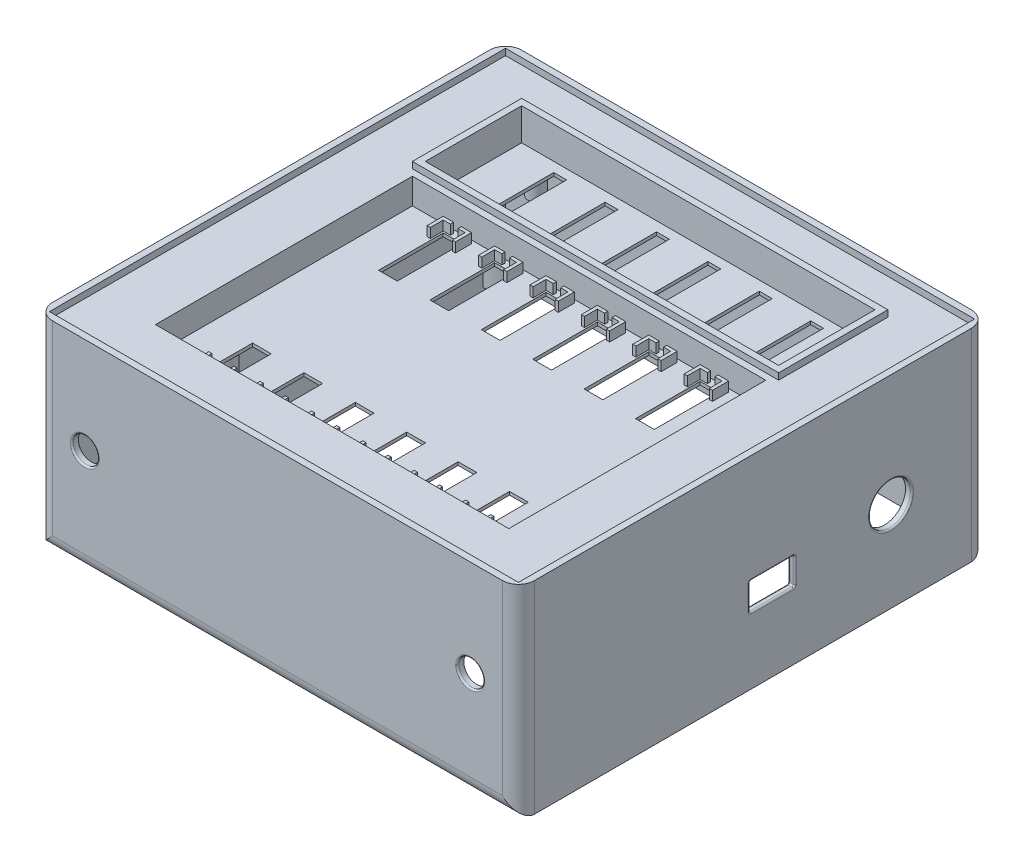
SolidWorks part; units mm, degrees
ref_plane "Front Plane" through (0, 0, 0) normal (0, 0, 1) x (1, 0, 0)
ref_plane "Top Plane" through (0, 0, 0) normal (0, 1, 0) x (1, 0, 0)
ref_plane "Right Plane" through (0, 0, 0) normal (1, 0, 0) x (0, 0, -1)
sketch "Sketch1" plane through (0, 0, 0) normal (0, 1, 0) x (1, 0, 0)
  line L1 (75, -65.5) -> (-75, -65.5)
  line L2 (75, -65.5) -> (75, 65.5)
  line L3 (75, 65.5) -> (-75, 65.5)
  line L4 (-75, -65.5) -> (-75, 65.5)
  line L5 (75, -65.5) -> (-75, 65.5) construction
  line L6 (75, 65.5) -> (-75, -65.5) construction
  point P0 (0, 0)
  dimension "D1" = 150
  dimension "D2" = 131
extrude "Boss-Extrude1" add sketch "Sketch1" against normal blind 63
sketch "Sketch2" plane through (0, 0, 0) normal (0, 1, 0) x (1, 0, 0)
  line L0 (0, -71.4639) -> (0, 67.3904) construction
  line L1 (75, 65.5) -> (-75, 65.5) construction
  line L2 (55, 20.5) -> (-55, 20.5)
  line L3 (55, 20.5) -> (55, 50.5)
  line L4 (55, 50.5) -> (-55, 50.5)
  line L5 (-55, 20.5) -> (-55, 50.5)
  line L6 (55, 20.5) -> (-55, 50.5) construction
  line L7 (55, 50.5) -> (-55, 20.5) construction
  point P2 (0, 35.5)
  dimension "D1" = 30
  dimension "D2" = 110
  dimension "D3" = 15
extrude "Cut-Extrude1" cut sketch "Sketch2" against normal blind 10
sketch "Sketch3" plane through (0, 0, 0) normal (0, 1, 0) x (1, 0, 0)
  line L0 (-73, 63.5) -> (-73, -63.5)
  line L1 (-73, -63.5) -> (73, -63.5)
  line L2 (73, -63.5) -> (73, 63.5)
  line L3 (73, 63.5) -> (-73, 63.5)
  line L8 (-75, 65.5) -> (-75, -65.5) construction
  line L9 (75, 65.5) -> (-75, 65.5) construction
  line L10 (75, -65.5) -> (75, 65.5) construction
  line L11 (-75, -65.5) -> (75, -65.5) construction
  line L12 (-57, 18.5) -> (57, 18.5)
  line L13 (57, 18.5) -> (57, 52.5)
  line L14 (57, 52.5) -> (-57, 52.5)
  line L15 (-57, 52.5) -> (-57, 18.5)
  line L18 (55, 50.5) -> (-55, 50.5) construction
  line L19 (-55, 50.5) -> (-55, 20.5) construction
  line L20 (-55, 20.5) -> (55, 20.5) construction
  line L21 (55, 20.5) -> (55, 50.5) construction
  dimension "D1" = 2
  dimension "D2" = 2
  dimension "D3" = 2
  dimension "D4" = 2
  dimension "D5" = 2
  dimension "D6" = 2
  dimension "D7" = 2
  dimension "D8" = 2
extrude "Cut-Extrude2" cut sketch "Sketch3" against normal blind 2
sketch "Sketch5" plane through (0, -2, 0) normal (0, 1, 0) x (1, 0, 0)
  line L0 (75, -65.5) -> (75, 65.5) construction
  line L1 (55, -63.5) -> (-55, -63.5)
  line L2 (55, -63.5) -> (55, 16.5)
  line L3 (55, 16.5) -> (-55, 16.5)
  line L4 (-55, -63.5) -> (-55, 16.5)
  line L5 (55, -63.5) -> (-55, 16.5) construction
  line L6 (55, 16.5) -> (-55, -63.5) construction
  line L7 (-75, 65.5) -> (-75, -65.5) construction
  line L8 (-73, -63.5) -> (73, -63.5) construction
  point P0 (0, -23.5)
  dimension "D1" = 80
  dimension "D2" = 110
  dimension "D3" = 20
  dimension "D4" = 20
  dimension "D5" = 0
extrude "Cut-Extrude3" cut sketch "Sketch5" against normal blind 8
sketch "Sketch6" plane through (0, -63, 0) normal (0, -1, 0) x (1, 0, 0)
  line L0 (75, 65.5) -> (75, -65.5) construction
  line L1 (-73, 63.5) -> (73, 63.5)
  line L2 (-73, 63.5) -> (-73, -63.5)
  line L3 (-73, -63.5) -> (73, -63.5)
  line L4 (73, 63.5) -> (73, -63.5)
  line L5 (-73, 63.5) -> (73, -63.5) construction
  line L6 (-73, -63.5) -> (73, 63.5) construction
  line L7 (75, -65.5) -> (-75, -65.5) construction
  point P0 (0, 0)
  dimension "D1" = 2
  dimension "D2" = 2
extrude "Cut-Extrude4" cut sketch "Sketch6" against normal blind 52
sketch "Sketch7" plane through (0, -10, 0) normal (0, 1, 0) x (1, 0, 0)
  line L0 (-55, 50.5) -> (-55, 20.5) construction
  line L1 (-42, 47.5) -> (-38, 47.5)
  line L2 (-42, 47.5) -> (-42, 22.5)
  line L3 (-42, 22.5) -> (-38, 22.5)
  line L4 (-38, 47.5) -> (-38, 22.5)
  line L5 (55, 50.5) -> (-55, 50.5) construction
  line L6 (55, 50.5) -> (-55, 50.5) construction
  line L7 (-26, 47.5) -> (-22, 47.5)
  line L8 (-26, 47.5) -> (-26, 22.5)
  line L9 (-26, 22.5) -> (-22, 22.5)
  line L10 (-22, 47.5) -> (-22, 22.5)
  line L11 (-10, 47.5) -> (-6, 47.5)
  line L12 (-10, 47.5) -> (-10, 22.5)
  line L13 (-10, 22.5) -> (-6, 22.5)
  line L14 (-6, 47.5) -> (-6, 22.5)
  line L15 (6, 47.5) -> (10, 47.5)
  line L16 (6, 47.5) -> (6, 22.5)
  line L17 (6, 22.5) -> (10, 22.5)
  line L18 (10, 47.5) -> (10, 22.5)
  line L19 (22, 47.5) -> (26, 47.5)
  line L20 (22, 47.5) -> (22, 22.5)
  line L21 (22, 22.5) -> (26, 22.5)
  line L22 (26, 47.5) -> (26, 22.5)
  line L23 (38, 47.5) -> (42, 47.5)
  line L24 (38, 47.5) -> (38, 22.5)
  line L25 (38, 22.5) -> (42, 22.5)
  line L26 (42, 47.5) -> (42, 22.5)
  dimension "D1" = 13
  dimension "D2" = 4
  dimension "D3" = 3
  dimension "D4" = 25
  dimension "D5" = 12
  dimension "D6" = 4
  dimension "D7" = 25
  dimension "D8" = 3
  dimension "D9" = 4
  dimension "D10" = 25
  dimension "D11" = 3
  dimension "D12" = 25
  dimension "D13" = 12
  dimension "D14" = 12
  dimension "D15" = 4
  dimension "D16" = 3
  dimension "D17" = 25
  dimension "D18" = 12
  dimension "D19" = 4
  dimension "D20" = 25
  dimension "D21" = 3
  dimension "D22" = 12
  dimension "D23" = 4
  dimension "D24" = 4
  dimension "D25" = 3
  dimension "D26" = 25
extrude "Cut-Extrude5" cut sketch "Sketch7" against normal blind 1.2
sketch "Sketch8" plane through (0, -10, 0) normal (0, 1, 0) x (1, 0, 0)
  line L0 (-40, 9.5911) -> (-40, -52.7056) construction
  line L1 (-24, 9.5911) -> (-24, -53.8329) construction
  line L2 (-8, 9.5911) -> (-8, -53.8329) construction
  line L3 (8, 9.5911) -> (8, -53.8329) construction
  line L4 (24, 9.5911) -> (24, -53.8329) construction
  line L5 (40, 9.5911) -> (40, -53.8329) construction
  line L6 (-49.171, -23.5) -> (50.2417, -23.5) construction
  line L7 (-73, -63.5) -> (73, -63.5) construction
  line L8 (-42.9103, -61) -> (-37.0897, -61)
  line L9 (-42.9103, -61) -> (-42.9103, -45.3557)
  line L10 (-42.9103, 14) -> (-37.0897, 14)
  line L11 (-37.0897, -61) -> (-37.0897, -45.3557)
  line L12 (-42.9103, -61) -> (-37.0897, 14) construction
  line L13 (-42.9103, 14) -> (-37.0897, -61) construction
  line L14 (-42.9103, -6.1263) -> (-37.0897, -6.1263)
  line L15 (-42.9103, -45.3557) -> (-37.0897, -45.3557)
  line L16 (-37.0897, -6.1263) -> (-37.0897, 14)
  line L17 (-42.9103, -6.1263) -> (-42.9103, 14)
  line L18 (-32, 9.5911) -> (-32, -46.68) construction
  line L19 (-21.0897, -61) -> (-21.0897, -45.3557)
  line L20 (-21.0897, -45.3557) -> (-26.9103, -45.3557)
  line L21 (-26.9103, -61) -> (-26.9103, -45.3557)
  line L22 (-21.0897, -61) -> (-26.9103, -61)
  line L23 (-21.0897, -6.1263) -> (-21.0897, 14)
  line L24 (-21.0897, -6.1263) -> (-26.9103, -6.1263)
  line L25 (-26.9103, -6.1263) -> (-26.9103, 14)
  line L26 (-21.0897, 14) -> (-26.9103, 14)
  line L27 (-16, 9.5911) -> (-16, -45.3557) construction
  line L28 (0, 9.5911) -> (0, -45.3557) construction
  line L29 (-10.9103, -61) -> (-5.0897, -61)
  line L30 (-5.0897, -61) -> (-5.0897, -45.3557)
  line L31 (-10.9103, -45.3557) -> (-5.0897, -45.3557)
  line L32 (-10.9103, -61) -> (-10.9103, -45.3557)
  line L33 (-10.9103, -6.1263) -> (-5.0897, -6.1263)
  line L34 (-5.0897, -6.1263) -> (-5.0897, 14)
  line L35 (-10.9103, 14) -> (-5.0897, 14)
  line L36 (-10.9103, -6.1263) -> (-10.9103, 14)
  line L37 (10.9103, -61) -> (10.9103, -45.3557)
  line L38 (10.9103, -45.3557) -> (5.0897, -45.3557)
  line L39 (5.0897, -61) -> (5.0897, -45.3557)
  line L40 (10.9103, -61) -> (5.0897, -61)
  line L41 (21.0897, -61) -> (26.9103, -61)
  line L42 (26.9103, -61) -> (26.9103, -45.3557)
  line L43 (21.0897, -45.3557) -> (26.9103, -45.3557)
  line L44 (21.0897, -61) -> (21.0897, -45.3557)
  line L45 (42.9103, -61) -> (42.9103, -45.3557)
  line L46 (42.9103, -45.3557) -> (37.0897, -45.3557)
  line L47 (37.0897, -61) -> (37.0897, -45.3557)
  line L48 (42.9103, -61) -> (37.0897, -61)
  line L49 (10.9103, -6.1263) -> (10.9103, 14)
  line L50 (10.9103, 14) -> (5.0897, 14)
  line L51 (5.0897, -6.1263) -> (5.0897, 14)
  line L52 (10.9103, -6.1263) -> (5.0897, -6.1263)
  line L53 (21.0897, -6.1263) -> (26.9103, -6.1263)
  line L54 (26.9103, -6.1263) -> (26.9103, 14)
  line L55 (21.0897, 14) -> (26.9103, 14)
  line L56 (21.0897, -6.1263) -> (21.0897, 14)
  line L57 (42.9103, -6.1263) -> (42.9103, 14)
  line L58 (42.9103, -6.1263) -> (37.0897, -6.1263)
  line L59 (37.0897, -6.1263) -> (37.0897, 14)
  line L60 (42.9103, 14) -> (37.0897, 14)
  point P14 (-40, -23.5)
  dimension "D1" = 75
  dimension "D2" = 40
  dimension "D3" = 8
  dimension "D4" = 8
  dimension "D5" = 8
extrude "Cut-Extrude6" cut sketch "Sketch8" against normal blind 1.2
sketch "Sketch9" plane through (0, -10, 0) normal (0, 1, 0) x (1, 0, 0)
  line L0 (-41.1603, 14.5) -> (-43.4103, 14.5)
  line L1 (-43.4103, 14.5) -> (-43.4103, 10.5)
  line L2 (-43.4103, 10.5) -> (-44.4103, 10.5)
  line L3 (-44.4103, 10.5) -> (-44.4103, 15.5)
  line L4 (-44.4103, 15.5) -> (-41.1603, 15.5)
  line L5 (-41.1603, 15.5) -> (-41.1603, 14.5)
  line L6 (-37.0897, 14) -> (-42.9103, 14) construction
  line L7 (-42.9103, 14) -> (-42.9103, -6.1263) construction
  line L8 (-40, -6.1263) -> (-40, 9.5642) construction
  line L9 (-42.9103, -6.1263) -> (-37.0897, -6.1263) construction
  line L10 (-24, 10.5) -> (-24, -7.9868) construction
  line L11 (-8, 10.5) -> (-8, -9.2113) construction
  line L12 (-32, 9.5642) -> (-32, -3.0888) construction
  line L13 (-16, 9.5642) -> (-16, -3.6136) construction
  line L14 (-44.4103, -23.5) -> (49.8597, -23.5) construction
  line L15 (-55, -63.5) -> (55, -63.5) construction
  line L16 (-35.5897, 15.5) -> (-38.8397, 15.5)
  line L17 (-35.5897, 10.5) -> (-35.5897, 15.5)
  line L18 (-36.5897, 10.5) -> (-35.5897, 10.5)
  line L19 (-36.5897, 14.5) -> (-36.5897, 10.5)
  line L20 (-38.8397, 14.5) -> (-36.5897, 14.5)
  line L21 (-38.8397, 15.5) -> (-38.8397, 14.5)
  line L22 (-44.4103, -62.5) -> (-41.1603, -62.5)
  line L23 (-44.4103, -57.5) -> (-44.4103, -62.5)
  line L24 (-43.4103, -57.5) -> (-44.4103, -57.5)
  line L25 (-43.4103, -61.5) -> (-43.4103, -57.5)
  line L26 (-41.1603, -61.5) -> (-43.4103, -61.5)
  line L27 (-41.1603, -62.5) -> (-41.1603, -61.5)
  line L28 (-35.5897, -57.5) -> (-35.5897, -62.5)
  line L29 (-36.5897, -57.5) -> (-35.5897, -57.5)
  line L30 (-36.5897, -61.5) -> (-36.5897, -57.5)
  line L31 (-38.8397, -61.5) -> (-36.5897, -61.5)
  line L32 (-38.8397, -62.5) -> (-38.8397, -61.5)
  line L33 (-35.5897, -62.5) -> (-38.8397, -62.5)
  line L34 (-19.5897, -57.5) -> (-19.5897, -62.5)
  line L35 (-20.5897, -57.5) -> (-19.5897, -57.5)
  line L36 (-20.5897, -61.5) -> (-20.5897, -57.5)
  line L37 (-22.8397, -61.5) -> (-20.5897, -61.5)
  line L38 (-22.8397, -62.5) -> (-22.8397, -61.5)
  line L39 (-19.5897, -62.5) -> (-22.8397, -62.5)
  line L40 (-27.4103, -57.5) -> (-28.4103, -57.5)
  line L41 (-27.4103, -61.5) -> (-27.4103, -57.5)
  line L42 (-25.1603, -61.5) -> (-27.4103, -61.5)
  line L43 (-25.1603, -62.5) -> (-25.1603, -61.5)
  line L44 (-28.4103, -62.5) -> (-25.1603, -62.5)
  line L45 (-28.4103, -57.5) -> (-28.4103, -62.5)
  line L46 (-19.5897, 15.5) -> (-22.8397, 15.5)
  line L47 (-19.5897, 10.5) -> (-19.5897, 15.5)
  line L48 (-20.5897, 10.5) -> (-19.5897, 10.5)
  line L49 (-20.5897, 14.5) -> (-20.5897, 10.5)
  line L50 (-22.8397, 14.5) -> (-20.5897, 14.5)
  line L51 (-22.8397, 15.5) -> (-22.8397, 14.5)
  line L52 (-28.4103, 10.5) -> (-28.4103, 15.5)
  line L53 (-27.4103, 10.5) -> (-28.4103, 10.5)
  line L54 (-27.4103, 14.5) -> (-27.4103, 10.5)
  line L55 (-25.1603, 14.5) -> (-27.4103, 14.5)
  line L56 (-25.1603, 15.5) -> (-25.1603, 14.5)
  line L57 (-28.4103, 15.5) -> (-25.1603, 15.5)
  line L58 (-11.4103, -57.5) -> (-12.4103, -57.5)
  line L59 (-11.4103, -61.5) -> (-11.4103, -57.5)
  line L60 (-9.1603, -61.5) -> (-11.4103, -61.5)
  line L61 (-9.1603, -62.5) -> (-9.1603, -61.5)
  line L62 (-12.4103, -62.5) -> (-9.1603, -62.5)
  line L63 (-12.4103, -57.5) -> (-12.4103, -62.5)
  line L64 (-4.5897, -61.5) -> (-4.5897, -57.5)
  line L65 (-6.8397, -61.5) -> (-4.5897, -61.5)
  line L66 (-6.8397, -62.5) -> (-6.8397, -61.5)
  line L67 (-3.5897, -62.5) -> (-6.8397, -62.5)
  line L68 (-3.5897, -57.5) -> (-3.5897, -62.5)
  line L69 (-4.5897, -57.5) -> (-3.5897, -57.5)
  line L70 (-12.4103, 10.5) -> (-12.4103, 15.5)
  line L71 (-11.4103, 10.5) -> (-12.4103, 10.5)
  line L72 (-11.4103, 14.5) -> (-11.4103, 10.5)
  line L73 (-9.1603, 14.5) -> (-11.4103, 14.5)
  line L74 (-9.1603, 15.5) -> (-9.1603, 14.5)
  line L75 (-12.4103, 15.5) -> (-9.1603, 15.5)
  line L76 (-4.5897, 10.5) -> (-3.5897, 10.5)
  line L77 (-4.5897, 14.5) -> (-4.5897, 10.5)
  line L78 (-6.8397, 14.5) -> (-4.5897, 14.5)
  line L79 (-6.8397, 15.5) -> (-6.8397, 14.5)
  line L80 (-3.5897, 15.5) -> (-6.8397, 15.5)
  line L81 (-3.5897, 10.5) -> (-3.5897, 15.5)
  line L82 (0, -55) -> (0, 55) construction
  line L83 (6.8397, -61.5) -> (4.5897, -61.5)
  line L84 (6.8397, -62.5) -> (6.8397, -61.5)
  line L85 (3.5897, -62.5) -> (6.8397, -62.5)
  line L86 (3.5897, -57.5) -> (3.5897, -62.5)
  line L87 (4.5897, -57.5) -> (3.5897, -57.5)
  line L88 (4.5897, -61.5) -> (4.5897, -57.5)
  line L89 (11.4103, -61.5) -> (11.4103, -57.5)
  line L90 (9.1603, -61.5) -> (11.4103, -61.5)
  line L91 (9.1603, -62.5) -> (9.1603, -61.5)
  line L92 (12.4103, -62.5) -> (9.1603, -62.5)
  line L93 (12.4103, -57.5) -> (12.4103, -62.5)
  line L94 (11.4103, -57.5) -> (12.4103, -57.5)
  line L95 (20.5897, -57.5) -> (19.5897, -57.5)
  line L96 (20.5897, -61.5) -> (20.5897, -57.5)
  line L97 (22.8397, -61.5) -> (20.5897, -61.5)
  line L98 (22.8397, -62.5) -> (22.8397, -61.5)
  line L99 (19.5897, -62.5) -> (22.8397, -62.5)
  line L100 (19.5897, -57.5) -> (19.5897, -62.5)
  line L101 (27.4103, -61.5) -> (27.4103, -57.5)
  line L102 (25.1603, -61.5) -> (27.4103, -61.5)
  line L103 (25.1603, -62.5) -> (25.1603, -61.5)
  line L104 (28.4103, -62.5) -> (25.1603, -62.5)
  line L105 (28.4103, -57.5) -> (28.4103, -62.5)
  line L106 (27.4103, -57.5) -> (28.4103, -57.5)
  line L107 (36.5897, -57.5) -> (35.5897, -57.5)
  line L108 (36.5897, -61.5) -> (36.5897, -57.5)
  line L109 (38.8397, -61.5) -> (36.5897, -61.5)
  line L110 (38.8397, -62.5) -> (38.8397, -61.5)
  line L111 (35.5897, -62.5) -> (38.8397, -62.5)
  line L112 (35.5897, -57.5) -> (35.5897, -62.5)
  line L113 (44.4103, -57.5) -> (44.4103, -62.5)
  line L114 (43.4103, -57.5) -> (44.4103, -57.5)
  line L115 (43.4103, -61.5) -> (43.4103, -57.5)
  line L116 (41.1603, -61.5) -> (43.4103, -61.5)
  line L117 (41.1603, -62.5) -> (41.1603, -61.5)
  line L118 (44.4103, -62.5) -> (41.1603, -62.5)
  line L119 (4.5897, 14.5) -> (4.5897, 10.5)
  line L120 (6.8397, 14.5) -> (4.5897, 14.5)
  line L121 (6.8397, 15.5) -> (6.8397, 14.5)
  line L122 (3.5897, 15.5) -> (6.8397, 15.5)
  line L123 (3.5897, 10.5) -> (3.5897, 15.5)
  line L124 (4.5897, 10.5) -> (3.5897, 10.5)
  line L125 (11.4103, 10.5) -> (12.4103, 10.5)
  line L126 (11.4103, 14.5) -> (11.4103, 10.5)
  line L127 (9.1603, 14.5) -> (11.4103, 14.5)
  line L128 (9.1603, 15.5) -> (9.1603, 14.5)
  line L129 (12.4103, 15.5) -> (9.1603, 15.5)
  line L130 (12.4103, 10.5) -> (12.4103, 15.5)
  line L131 (19.5897, 10.5) -> (19.5897, 15.5)
  line L132 (20.5897, 10.5) -> (19.5897, 10.5)
  line L133 (20.5897, 14.5) -> (20.5897, 10.5)
  line L134 (22.8397, 14.5) -> (20.5897, 14.5)
  line L135 (22.8397, 15.5) -> (22.8397, 14.5)
  line L136 (19.5897, 15.5) -> (22.8397, 15.5)
  line L137 (27.4103, 10.5) -> (28.4103, 10.5)
  line L138 (27.4103, 14.5) -> (27.4103, 10.5)
  line L139 (25.1603, 14.5) -> (27.4103, 14.5)
  line L140 (25.1603, 15.5) -> (25.1603, 14.5)
  line L141 (28.4103, 15.5) -> (25.1603, 15.5)
  line L142 (28.4103, 10.5) -> (28.4103, 15.5)
  line L143 (35.5897, 10.5) -> (35.5897, 15.5)
  line L144 (36.5897, 10.5) -> (35.5897, 10.5)
  line L145 (36.5897, 14.5) -> (36.5897, 10.5)
  line L146 (38.8397, 14.5) -> (36.5897, 14.5)
  line L147 (38.8397, 15.5) -> (38.8397, 14.5)
  line L148 (35.5897, 15.5) -> (38.8397, 15.5)
  line L149 (44.4103, 15.5) -> (41.1603, 15.5)
  line L150 (44.4103, 10.5) -> (44.4103, 15.5)
  line L151 (43.4103, 10.5) -> (44.4103, 10.5)
  line L152 (43.4103, 14.5) -> (43.4103, 10.5)
  line L153 (41.1603, 14.5) -> (43.4103, 14.5)
  line L154 (41.1603, 15.5) -> (41.1603, 14.5)
  dimension "D1" = 0.5
  dimension "D2" = 0.5
  dimension "D3" = 1
  dimension "D4" = 1
  dimension "D5" = 3.25
  dimension "D6" = 5
  dimension "D7" = 8
  dimension "D8" = 8
  dimension "D9" = 8
  dimension "D10" = 8
  dimension "D11" = 40
extrude "Boss-Extrude2" add sketch "Sketch9" along normal blind 3
sketch "Sketch10" plane through (0, -11, 0) normal (0, -1, 0) x (1, 0, 0)
  circle A0 centre (48, -48) radius 2.5
  circle A1 centre (-48, -48) radius 2.5
  circle A2 centre (48, 48) radius 2.5
  circle A3 centre (-48, 48) radius 2.5
  dimension "D5" = 5
  dimension "D8" = 5
  dimension "D11" = 5
  dimension "D14" = 5
extrude "Boss-Extrude3" add sketch "Sketch10" along normal blind 8.5
fillet "Fillet1" radius 2 1 edges at (48, -11, -50.5)
fillet "Fillet2" radius 2 3 edges at (48, -11, 45.5) (-48, -11, 45.5) (-48, -11, -50.5)
sketch "Sketch11" plane through (0, -19.5, 0) normal (0, -1, 0) x (1, 0, 0)
  circle A0 centre (48, -48) radius 1.5
  dimension "D1" = 3
extrude "Cut-Extrude7" cut sketch "Sketch11" against normal blind 5
mirror "Mirror1" about plane through (0, 0, 0) normal (1, 0, 0) of "Cut-Extrude7"
sketch "Sketch12" plane through (0, -19.5, 0) normal (0, -1, 0) x (1, 0, 0)
  circle A0 centre (48, 48) radius 1.5
  dimension "D1" = 3
extrude "Cut-Extrude8" cut sketch "Sketch12" against normal blind 5
mirror "Mirror3" about plane through (0, 0, 0) normal (1, 0, 0) of "Cut-Extrude8"
sketch "Sketch13" plane through (0, 0, 0) normal (0, 1, 0) x (1, 0, 0)
  line L1 (75, -65.5) -> (-75, -65.5)
  line L2 (75, -65.5) -> (75, -80.5)
  line L3 (75, -80.5) -> (-75, -80.5)
  line L4 (-75, -65.5) -> (-75, -80.5)
  dimension "D1" = 15
  dimension "D2" = 150
extrude "Boss-Extrude4" add sketch "Sketch13" against normal blind 63
sketch "Sketch14" plane through (0, 0, 0) normal (0, 1, 0) x (1, 0, 0)
  line L1 (73, -63.5) -> (-73, -63.5)
  line L2 (73, -63.5) -> (73, -78.5)
  line L3 (73, -78.5) -> (-73, -78.5)
  line L4 (-73, -63.5) -> (-73, -78.5)
  dimension "D1" = 15
  dimension "D2" = 146
extrude "Cut-Extrude9" cut sketch "Sketch14" against normal blind 2
sketch "Sketch15" plane through (0, -63, 0) normal (0, -1, 0) x (1, 0, 0)
  line L1 (-73, 63.5) -> (73, 63.5)
  line L2 (-73, 63.5) -> (-73, 78.5)
  line L3 (-73, 78.5) -> (73, 78.5)
  line L4 (73, 63.5) -> (73, 78.5)
  dimension "D1" = 15
  dimension "D2" = 146
extrude "Cut-Extrude10" cut sketch "Sketch15" against normal blind 52
sketch "Sketch17" plane through (0, -63, 0) normal (0, -1, 0) x (1, 0, 0)
  line L0 (73, -63.5) -> (73, 78.5) construction
  line L1 (-73, -63.5) -> (73, -63.5) construction
  line L2 (73, -63.5) -> (66, -63.5)
  line L3 (73, -63.5) -> (73, -56.5)
  line L4 (-73, 78.5) -> (-73, -63.5) construction
  line L5 (-73, -63.5) -> (73, -63.5) construction
  line L6 (-66, -63.5) -> (-73, -63.5)
  line L7 (-73, -63.5) -> (-73, -56.5)
  line L8 (73, 78.5) -> (-73, 78.5) construction
  line L9 (-66, 78.5) -> (-73, 78.5)
  line L10 (-73, 78.5) -> (-73, 71.5)
  line L11 (73, 78.5) -> (73, 71.5)
  line L12 (73, 78.5) -> (66, 78.5)
  arc A0 (73, -56.5) -> (66, -63.5) centre (73, -63.5) ccw
  arc A1 (-73, -56.5) -> (-66, -63.5) centre (-73, -63.5) cw
  arc A2 (-73, 71.5) -> (-66, 78.5) centre (-73, 78.5) ccw
  arc A3 (73, 71.5) -> (66, 78.5) centre (73, 78.5) cw
  dimension "D1" = 7
  dimension "D2" = 7
  dimension "D3" = 7
  dimension "D4" = 7
extrude "Boss-Extrude5" add sketch "Sketch17" against normal blind 10
sketch "Sketch18" plane through (0, -63, 0) normal (0, -1, 0) x (1, 0, 0)
  line L0 (-73, -63.5) -> (73, -63.5) construction
  line L1 (73, -63.5) -> (-73, -63.5)
  line L2 (73, -63.5) -> (73, 78.5)
  line L3 (73, 78.5) -> (-73, 78.5)
  line L4 (-73, -63.5) -> (-73, 78.5)
  line L5 (-73, 78.5) -> (-73, -63.5) construction
  line L6 (66, 78.5) -> (-66, 78.5) construction
  line L7 (73, -56.5) -> (73, 71.5) construction
  dimension "D1" = 0
  dimension "D2" = 0
  dimension "D3" = 0
extrude "Cut-Extrude11" cut sketch "Sketch18" against normal blind 2
sketch "Sketch19" plane through (0, -61, 0) normal (0, -1, 0) x (1, 0, 0)
  line L0 (-73, -63.5) -> (73, -63.5) construction
  line L1 (73, -63.5) -> (73, 78.5) construction
  circle A0 centre (70, -60.5) radius 1.5
  dimension "D1" = 3
  dimension "D2" = 3
  dimension "D3" = 3
extrude "Cut-Extrude12" cut sketch "Sketch19" against normal blind 5
sketch "Sketch20" plane through (0, -61, 0) normal (0, -1, 0) x (1, 0, 0)
  line L0 (-73, -63.5) -> (-66, -63.5) construction
  line L3 (-73, 78.5) -> (-73, -63.5) construction
  line L4 (-66, 78.5) -> (-73, 78.5) construction
  line L6 (-73, 78.5) -> (-73, 71.5) construction
  line L7 (73, 78.5) -> (66, 78.5) construction
  line L9 (73, -63.5) -> (73, 78.5) construction
  circle A0 centre (-70, -60.5) radius 1.5
  circle A1 centre (-70, 75.5) radius 1.5
  circle A2 centre (70, 75.5) radius 1.5
  dimension "D1" = 3
  dimension "D4" = 3
  dimension "D7" = 3
  dimension "D2" = 3
  dimension "D3" = 3
  dimension "D5" = 3
  dimension "D6" = 3
  dimension "D8" = 3
  dimension "D9" = 3
sketch "Sketch21" plane through (75, 0, 0) normal (1, 0, 0) x (0, 0, -1)
  line L0 (65.5, -63) -> (65.5, 0) construction
  line L1 (-80.5, 0) -> (65.5, 0) construction
  circle A0 centre (35.5, -35) radius 6.5
  dimension "D1" = 13
  dimension "D2" = 30
  dimension "D3" = 35
extrude "Cut-Extrude14" cut sketch "Sketch21" against normal blind 5
fillet "Fillet3" radius 0.5 1 edges at (75, -35, -42)
sketch "Sketch22" plane through (0, 0, 80.5) normal (0, 0, 1) x (1, 0, 0)
  line L0 (75, -63) -> (75, 0) construction
  line L1 (-75, -63) -> (-75, 0) construction
  line L2 (-75, 0) -> (75, 0) construction
  circle A0 centre (60, -30) radius 4
  circle A1 centre (-60, -30) radius 4
  dimension "D1" = 8
  dimension "D2" = 8
  dimension "D3" = 15
  dimension "D4" = 15
  dimension "D5" = 30
  dimension "D6" = 30
extrude "Cut-Extrude15" cut sketch "Sketch22" against normal blind 5
fillet "Fillet4" radius 0.5 2 edges at (-56, -30, 80.5) (64, -30, 80.5)
sketch "Sketch23" plane through (75, 0, 0) normal (1, 0, 0) x (0, 0, -1)
  line L1 (-8.5, -42.25) -> (5.5, -42.25)
  line L2 (-8.5, -42.25) -> (-8.5, -33.75)
  line L3 (-8.5, -33.75) -> (5.5, -33.75)
  line L4 (5.5, -42.25) -> (5.5, -33.75)
  line L5 (-8.5, -42.25) -> (5.5, -33.75) construction
  line L6 (-8.5, -33.75) -> (5.5, -42.25) construction
  line L8 (-80.5, -63) -> (65.5, -63) construction
  line L9 (65.5, -63) -> (65.5, 0) construction
  point P0 (-1.5, -38)
  dimension "D1" = 8.5
  dimension "D2" = 14
  dimension "D3" = 25
  dimension "D4" = 60
extrude "Cut-Extrude16" cut sketch "Sketch23" against normal blind 5
fillet "Fillet5" radius 0.5 12 edges at (73, -38, -5.5) (73, -38, 8.5) (75, -38, -5.5) (73, -42.25, 1.5) (74, -42.25, -5.5) (75, -42.25, 1.5) (74, -42.25, 8.5) (73, -33.75, 1.5) (74, -33.75, 8.5) (75, -33.75, 1.5) (74, -33.75, -5.5) (75, -38, 8.5)
fillet "Fillet7" radius 5 6 edges at (0, -63, -65.5) (0, -63, 80.5) (-75, -31.5, -65.5) (75, -31.5, -65.5) (75, -31.5, 80.5) (-75, -31.5, 80.5)
sketch "Sketch24" plane through (0, 0, -65.5) normal (0, 0, -1) x (-1, 0, 0)
  line L0 (-70, 0) -> (70, 0) construction
  line L1 (-70, 0) -> (-70, -58) construction
  line L2 (0, 34.65) -> (0, -34.65) construction
  line L3 (-70, -58) -> (70, -58) construction
  circle A0 centre (-56, -14) radius 3.5
  circle A1 centre (56, -14) radius 3.5
  circle A2 centre (-56, -44) radius 3.5
  circle A3 centre (56, -44) radius 3.5
  dimension "D1" = 7
  dimension "D4" = 7
  dimension "D2" = 14
  dimension "D3" = 14
  dimension "D5" = 14
  dimension "D6" = 14
extrude "Boss-Extrude6" add sketch "Sketch24" along normal blind 2
extrude "Cut-Extrude17" cut sketch "Sketch20" against normal blind 5
